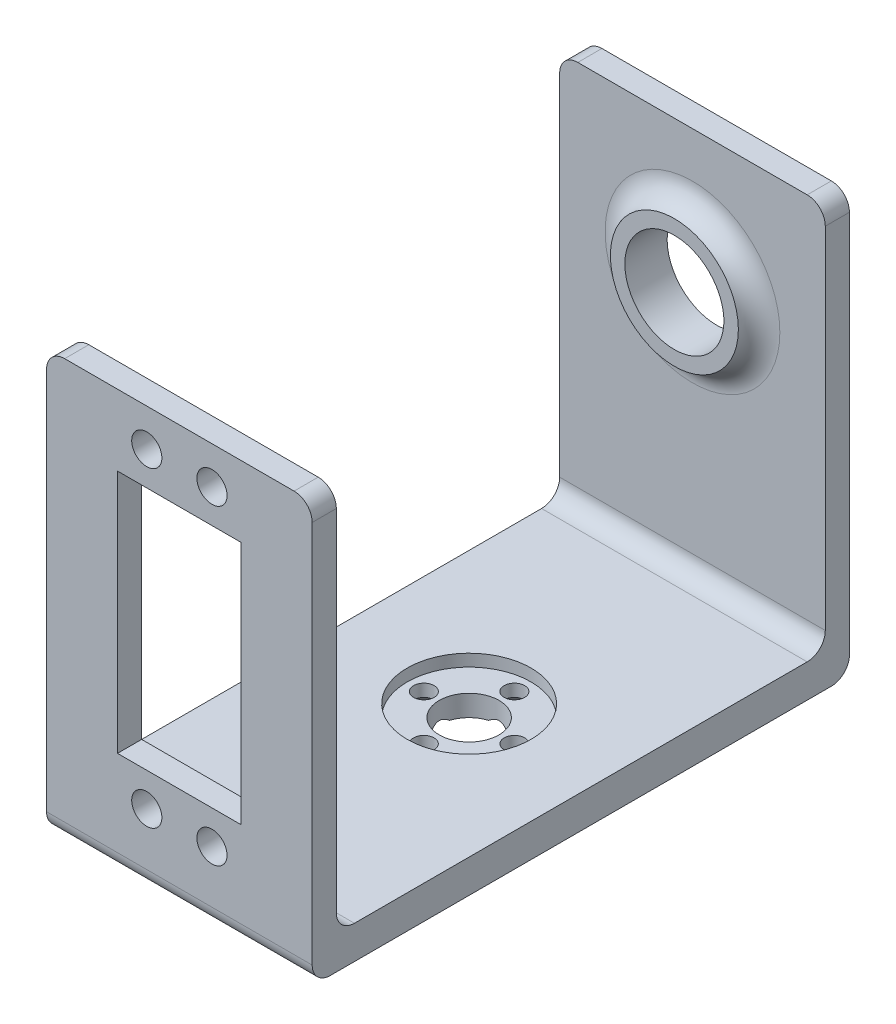
SolidWorks part; units mm, degrees
ref_plane "Plan de face" through (0, 0, 0) normal (0, 0, 1) x (1, 0, 0)
ref_plane "Plan de dessus" through (0, 0, 0) normal (0, 1, 0) x (1, 0, 0)
ref_plane "Plan de droite" through (0, 0, 0) normal (1, 0, 0) x (0, 0, -1)
sketch "Esquisse1" plane through (0, 0, 0) normal (0, 0, 1) x (1, 0, 0)
  line L8 (0.25, -20.25) -> (0.25, 20.25)
  line L9 (0.25, 20.25) -> (-20.25, 20.25)
  line L10 (-20.25, 20.25) -> (-20.25, -20.25)
  line L11 (-20.25, -20.25) -> (0.25, -20.25)
  line L12 (0.25, -20.25) -> (0.25, 20.25)
  line L13 (0.25, 20.25) -> (-20.25, 20.25)
  line L14 (-20.25, 20.25) -> (-20.25, -20.25)
  line L15 (-20.25, -20.25) -> (0.25, -20.25)
  line L20 (12, -32) -> (12, 32)
  line L21 (12, 32) -> (-32, 32)
  line L22 (-32, 32) -> (-32, -32)
  line L23 (-32, -32) -> (12, -32)
  line L24 (12, -32) -> (12, 32)
  line L25 (12, 32) -> (-32, 32)
  line L26 (-32, 32) -> (-32, -32)
  line L27 (-32, -32) -> (12, -32)
  dimension "D1" = 0.25
  dimension "D2" = 12
extrude "Boss.-Extru.1" add sketch "Esquisse1" against normal blind 4 from vertex at -3
sketch "Esquisse2" plane through (12, 0, 0) normal (1, 0, 0) x (0, 0, -1)
  line L1 (61, -32) -> (41, -32) construction
  line L2 (41, -37.5) -> (61, -37.5)
  line L3 (3, -37.5) -> (92, -37.5)
  line L4 (88, -32) -> (7, -32)
  line L8 (92, 2) -> (92, 18) construction
  line L9 (92, -37.5) -> (92, 32)
  line L10 (88, -32) -> (88, 32)
  line L11 (88, 32) -> (92, 32)
  line L12 (7, 32) -> (3, 32) construction
  line L14 (7, -32) -> (7, 32) construction
  line L15 (3, -32) -> (3, -28.4434)
  line L16 (3, -32) -> (3, 32) construction
  line L17 (3, -28.4434) -> (7, -28.4434)
  line L18 (7, -28.4434) -> (7, -32)
  line L19 (3, -37.5) -> (3, -32)
  dimension "D2" = 4
  dimension "D1" = 3.5
extrude "Boss.-Extru.2" add sketch "Esquisse2" against normal up to surface (44 mm away) up to face at (-32, 0, -5)
sketch "Esquisse3" plane through (0, 0, -92) normal (0, 0, -1) x (-1, 0, 0)
  circle A2 centre (10, 10) radius 8.2
  circle A3 centre (10, 10) radius 8.2
  dimension "D1" = 0.2
extrude "Enlèv. mat.-Extru.1" cut sketch "Esquisse3" against normal up to next
sketch "Esquisse4" plane through (0, 0, -88) normal (0, 0, 1) x (1, 0, 0)
  circle A0 centre (-10, 10) radius 8.2 construction
  circle A1 centre (-10, 10) radius 8.2
  circle A2 centre (-10, 10) radius 10.6
  dimension "D1" = 2.4
extrude "Boss.-Extru.3" add sketch "Esquisse4" along normal blind 3
fillet "Congé1" radius 4 1 edges at (0.6, 10, -88)
fillet "Congé2" radius 3 8 edges at (-32, 32, -90) (12, 32, -90) (-32, 32, -5) (12, 32, -5) (-10, -37.5, -92) (-10, -32, -88) (-10, -37.5, -3) (-10, -32, -7)
sketch "Esquisse5" plane through (0, 0, -7) normal (0, 0, -1) x (-1, 0, 0)
  arc A0 (3.4126, 28) -> (5.7874, 28) centre (4.6, 25.8) ccw construction
  arc A1 (14.2126, 28) -> (16.5874, 28) centre (15.4, 25.8) ccw construction
  arc A2 (5.7874, -28) -> (3.4126, -28) centre (4.6, -25.8) ccw construction
  arc A3 (16.5874, -28) -> (14.2126, -28) centre (15.4, -25.8) ccw construction
  circle A4 centre (4.6, 25.8) radius 2.5
  circle A5 centre (15.4, 25.8) radius 2.5
  circle A6 centre (4.6, -25.8) radius 2.5
  circle A7 centre (15.4, -25.8) radius 2.5
  point P12 (-15.4, 25.8)
  point P14 (-3.7027, 28)
  point P16 (-16.7354, -28)
  point P18 (-3.5357, -28)
extrude "Enlèv. mat.-Extru.2" cut sketch "Esquisse5" against normal up to next
sketch "Esquisse6" plane through (0, -32, 0) normal (0, 1, 0) x (1, 0, 0)
  circle A2 centre (-10, 51) radius 10.25
  circle A3 centre (-10, 51) radius 10.25
  dimension "D1" = 0.25
extrude "Enlèv. mat.-Extru.3" cut sketch "Esquisse6" against normal up to surface (2 mm away)
sketch "Esquisse7" plane through (0, -37.5, 0) normal (0, -1, 0) x (1, 0, 0)
  circle A2 centre (-10, -51) radius 4.95
  circle A3 centre (-10, -51) radius 4.95
  dimension "D1" = 0.25
extrude "Enlèv. mat.-Extru.4" cut sketch "Esquisse7" against normal up to next
hole_wizard "Fraisage pour vis à tête fraisée M31" positions "Esquisse8" profile "Esquisse9" countersink size "M3" standard "ISO" end condition through all
sketch "Esquisse8" plane through (0, -37.5, 0) normal (0, -1, 0) x (-1, 0, 0)
  point P0 (10, 58.5)
  point P3 (17.5, 51)
  point P6 (10, 43.5)
  point P9 (2.5, 51)
sketch "Esquisse9" plane through (-10, -37.5, -58.5) normal (1, 0, 0) x (0, 0, -1)
  line L0 (0, 0) -> (0, 69.5)
  line L1 (0, 69.5) -> (1.7, 69.5)
  line L2 (1.7, 69.5) -> (1.7, 1.45)
  line L3 (1.7, 1.45) -> (3.15, 0)
  line L5 (3.15, 0) -> (0, 0)
  line L6 (-1.7, 1.45) -> (-3.15, 0) construction
  line L11 (0, -6.35) -> (0, 107.95) construction
  dimension "Diamètre du perçage jusqu'au prochain" = 3.4
  dimension "Profondeur du perçage jusqu'au prochain" = 69.5
  dimension "Diamètre du fraisage entrant" = 6.3
  dimension "Angle du fraisage entrant" = 90
